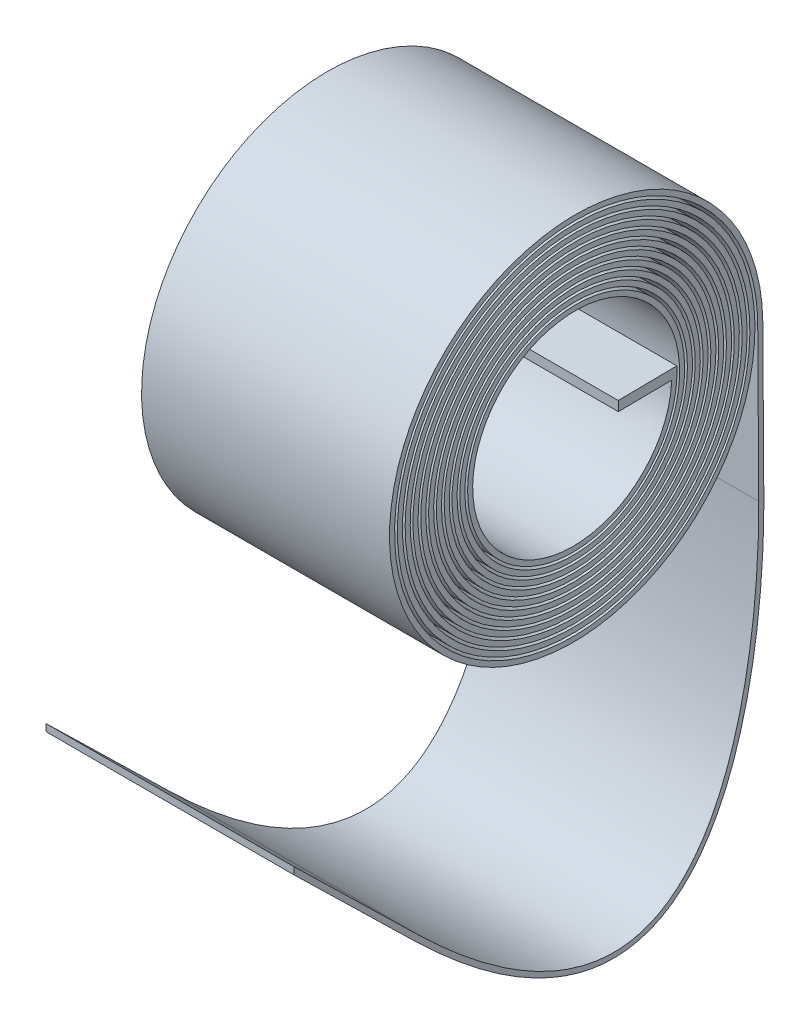
SolidWorks part; units mm, degrees
ref_plane "Front Plane" through (0, 0, 0) normal (0, 0, 1) x (1, 0, 0)
ref_plane "Top Plane" through (0, 0, 0) normal (0, 1, 0) x (1, 0, 0)
ref_plane "Right Plane" through (0, 0, 0) normal (1, 0, 0) x (0, 0, -1)
sketch "Sketch1" plane through (0, 0, 0) normal (1, 0, 0) x (0, 0, -1)
  circle A0 centre (0, 0) radius 2.5
  dimension "D1" = 5
curve "Helix/Spiral1"
sketch "Sketch2" plane through (0, 0, 0) normal (1, 0, 0) x (0, 0, -1)
  line L0 (2.5, 0) -> (2.63, 0.0017)
  line L2 (4.7, 0) -> (4.83, 0.0009)
  spline S0 degree 3 poles (-439.0072, -897.1615) (-56.85, 58.0039) (7.9525, 8.6548) (1.9311, -1.6856) (1.5943, -2.015) (0.7951, -2.4552) (0.3338, -2.5653) (-0.5842, -2.5317) (-1.0395, -2.3879) (-1.8147, -1.8837) (-2.1335, -1.5239) (-2.5418, -0.6873) (-2.6308, -0.2117) (-2.5504, 0.722) (-2.381, 1.1787) (-1.8283, 1.9431) (-1.4457, 2.2498) (-0.5729, 2.6237) (-0.084, 2.6904) (0.863, 2.5615) (1.3196, 2.366) (2.0704, 1.7647) (2.3634, 1.3597) (2.7003, 0.4521) (2.7437, -0.0491) (2.5648, -1.0068) (2.3429, -1.4619) (1.693, -2.196) (1.2659, -2.4739) (0.3252, -2.7713) (-0.1872, -2.7902) (-1.153, -2.5601) (-1.605, -2.3113) (-2.3194, -1.6131) (-2.5808, -1.1646) (-2.8362, -0.1923) (-2.8297, 0.33) (-2.5471, 1.3011) (-2.2713, 1.7484) (-1.5251, 2.4402) (-1.0557, 2.6836) (-0.0539, 2.8946) (0.4771, 2.8618) (1.4506, 2.5256) (1.8918, 2.2227) (2.5579, 1.4291) (2.7818, 0.9395) (2.9461, -0.0898) (2.8861, -0.6281) (2.4955, -1.6011) (2.1653, -2.0344) (1.3251, -2.6719) (0.8161, -2.875) (-0.2384, -2.9904) (-0.7826, -2.9024) (-1.752, -2.4566) (-2.1759, -2.0993) (-2.7817, -1.2133) (-2.9626, -0.6859) (-3.027, 0.3916) (-2.9104, 0.9402) (-2.4087, 1.9029) (-2.0244, 2.3158) (-1.0939, 2.8869) (-0.549, 3.0443) (0.549, 3.0557) (1.1004, 2.9097) (2.0533, 2.3519) (2.4534, 1.9409) (2.9869, 0.9671) (3.1195, 0.4057) (3.0762, -0.71) (2.9002, -1.2628) (2.286, -2.2026) (1.8486, -2.5884) (0.833, -3.0814) (0.2563, -3.1879) (-0.8744, -3.088) (-1.4268, -2.8817) (-2.3503, -2.2111) (-2.72, -1.7476) (-3.1697, -0.692) (-3.249, -0.1012) (-3.091, 1.0416) (-2.854, 1.592) (-2.1271, 2.4958) (-1.6382, 2.8479) (-0.5442, 3.2515) (0.0593, 3.3024) (1.2112, 3.085) (1.7579, 2.8169) (2.6387, 2.034) (2.9715, 1.5203) (3.3263, 0.3901) (3.3478, -0.2248) (3.0696, -1.3826) (2.7703, -1.9239) (1.932, -2.7784) (1.3942, -3.0903) (0.23, -3.3937) (-0.3949, -3.3848) (-1.5554, -3.0447) (-2.0895, -2.714) (-2.9142, -1.8211) (-3.2038, -1.2601) (-3.4533, -0.0641) (-3.413, 0.5691) (-3.0101, 1.7291) (-2.6481, 2.2541) (-1.7015, 3.0458) (-1.1181, 3.3114) (0.107, 3.5047) (0.7471, 3.4321) (1.903, 2.9657) (2.4172, 2.5725) (3.1726, 1.5732) (3.4126, 0.9686) (3.5474, -0.283) (3.4419, -0.9282) (2.9114, -2.0767) (2.4871, -2.5783) (1.4366, -3.294) (0.8117, -3.5071) (-0.4635, -3.5812) (-1.1121, -3.4421) (-2.2495, -2.8471) (-2.7366, -2.3921) (-3.4095, -1.2918) (-3.5943, -0.648) (-3.6057, 0.648) (-3.4324, 1.2982) (-2.7728, 2.421) (-2.2874, 2.8918) (-1.139, 3.5186) (-0.4775, 3.6737) (0.8359, 3.6206) (1.486, 3.4125) (2.5905, 2.6884) (3.0432, 2.1732) (3.6209, 0.9787) (3.7449, 0.3009) (3.6257, -1.0268) (3.3825, -1.6749) (2.5939, -2.7574) (2.0496, -3.1903) (0.811, -3.7157) (0.1184, -3.8075) (-1.2202, -3.6206) (-1.8644, -3.342) (-2.9213, -2.4894) (-3.3324, -1.9167) (-3.8027, -0.6363) (-3.8611, 0.0695) (-3.6051, 1.4156) (-3.2909, 2.0539) (-2.3751, 3.0814) (-1.7747, 3.4691) (-0.455, 3.8814) (0.2624, 3.9054) (1.6123, 3.579) (2.2428, 3.2292) (3.2373, 2.2509) (3.5998, 1.6239) (3.9513, 0.2676) (3.9398, -0.4598) (3.5423, -1.8098) (3.1567, -2.4305) (2.1171, -3.3882) (1.4645, -3.7239) (0.0743, -4.0121) (-0.6612, -3.9642) (-2.0076, -3.4946) (-2.6165, -3.0735) (-3.5338, -1.9738) (-3.8409, -1.2967) (-4.0633, 0.1242) (-3.9781, 0.8661) (-3.436, 2.2049) (-2.9796, 2.8) (-1.8213, 3.6733) (-1.121, 3.9503) (0.3277, 4.1045) (1.0739, 3.9814) (2.4013, 3.3663) (2.9806, 2.875) (3.8063, 1.6598) (4.0516, 0.9376) (4.1354, -0.5354) (3.9738, -1.2841) (3.2855, -2.5961) (2.7598, -3.1575) (1.4896, -3.9322) (0.7469, -4.1443) (-0.7469, -4.1557) (-1.4961, -3.955) (-2.7886, -3.1936) (-3.3302, -2.634) (-4.0504, -1.311) (-4.2279, -0.5494) (-4.1651, 0.9618) (-3.9249, 1.7093) (-3.0907, 2.9783) (-2.4979, 3.4981) (-1.1243, 4.1604) (-0.3455, 4.302) (1.1793, 4.1633) (1.9231, 3.8832) (3.1646, 2.9767) (3.6605, 2.3515) (4.2617, 0.93) (4.3661, 0.1356) (4.1501, -1.3989) (3.8299, -2.1368) (2.8518, -3.3467) (2.1952, -3.8169) (0.7284, -4.3539) (-0.0797, -4.4199) (-1.62, -4.1252) (-2.3499, -3.7649) (-3.5241, -2.7161) (-3.9667, -2.0291) (-4.4364, -0.52) (-4.4629, 0.3) (-4.0885, 1.842) (-3.6881, 2.5617) (-2.5698, 3.6962) (-1.8535, 4.1092) (-0.3052, 4.5089) (0.5248, 4.4949) (2.0642, 4.0398) (2.7716, 3.5994) (3.8622, 2.4131) (4.244, 1.6688) (4.5708, 0.0845) (4.5154, -0.7533) (3.9791, -2.2861) (3.499, -2.9788) (2.2462, -4.0217) (1.4753, -4.3704) (0.2627, -4.559) (-0.1504, -4.567) (-0.9645, -4.4723) (-1.3656, -4.3697) (-2.1264, -4.0607) (-2.4862, -3.8544) (-3.1383, -3.3528) (-3.4306, -3.0574) (-3.9263, -2.3988) (-4.1296, -2.0355) (-4.4321, -1.2671) (-4.5313, -0.862) (-4.6181, -0.0392) (-4.6057, 0.3785) (-4.4696, 1.1962) (-4.346, 1.5962) (-3.9961, 2.3494) (-3.7699, 2.7025) (-3.2308, 3.3363) (-2.9179, 3.6168) (-2.228, 4.0847) (-1.851, 4.272) (-1.0599, 4.5394) (-0.6458, 4.6195) (0.1896, 4.6662) (0.6108, 4.6329) (1.4299, 4.4548) (1.8277, 4.3101) (2.571, 3.9193) (2.9164, 3.6733) (3.5297, 3.0973) (3.7975, 2.7674) (4.2357, 2.0475) (4.4061, 1.6574) (9.2324, -15.3331) (-77.8687, -58.615) (-418.7177, 905.7456) knots -0.190695 -0.190695 -0.190695 -0.190695 0.007812 0.007812 0.015625 0.015625 0.023437 0.023437 0.03125 0.03125 0.039062 0.039062 0.046875 0.046875 0.054687 0.054687 0.0625 0.0625 0.070312 0.070312 0.078125 0.078125 0.085937 0.085937 0.09375 0.09375 0.101562 0.101562 0.109375 0.109375 0.117187 0.117187 0.125 0.125 0.132812 0.132812 0.140625 0.140625 0.148438 0.148438 0.15625 0.15625 0.164062 0.164062 0.171875 0.171875 0.179688 0.179688 0.1875 0.1875 0.195312 0.195312 0.203125 0.203125 0.210938 0.210938 0.21875 0.21875 0.226562 0.226562 0.234375 0.234375 0.242188 0.242188 0.25 0.25 0.257812 0.257812 0.265625 0.265625 0.273438 0.273438 0.28125 0.28125 0.289062 0.289062 0.296875 0.296875 0.304688 0.304688 0.3125 0.3125 0.320312 0.320312 0.328125 0.328125 0.335938 0.335938 0.34375 0.34375 0.351562 0.351562 0.359375 0.359375 0.367188 0.367188 0.375 0.375 0.382812 0.382812 0.390625 0.390625 0.398438 0.398438 0.40625 0.40625 0.414062 0.414062 0.421875 0.421875 0.429688 0.429688 0.4375 0.4375 0.445312 0.445312 0.453125 0.453125 0.460938 0.460938 0.46875 0.46875 0.476562 0.476562 0.484375 0.484375 0.492188 0.492188 0.5 0.5 0.507812 0.507812 0.515625 0.515625 0.523438 0.523438 0.53125 0.53125 0.539062 0.539062 0.546875 0.546875 0.554688 0.554688 0.5625 0.5625 0.570312 0.570312 0.578125 0.578125 0.585938 0.585938 0.59375 0.59375 0.601562 0.601562 0.609375 0.609375 0.617188 0.617188 0.625 0.625 0.632812 0.632812 0.640625 0.640625 0.648438 0.648438 0.65625 0.65625 0.664062 0.664062 0.671875 0.671875 0.679688 0.679688 0.6875 0.6875 0.695312 0.695312 0.703125 0.703125 0.710938 0.710938 0.71875 0.71875 0.726562 0.726562 0.734375 0.734375 0.742188 0.742188 0.75 0.75 0.757812 0.757812 0.765625 0.765625 0.773438 0.773438 0.78125 0.78125 0.789062 0.789062 0.796875 0.796875 0.804688 0.804688 0.8125 0.8125 0.820312 0.820312 0.828125 0.828125 0.835938 0.835938 0.84375 0.84375 0.851562 0.851562 0.859375 0.859375 0.867188 0.867188 0.875 0.875 0.882812 0.882812 0.890625 0.890625 0.898438 0.898438 0.90625 0.90625 0.914062 0.914062 0.921875 0.921875 0.929688 0.929688 0.933594 0.933594 0.9375 0.9375 0.941406 0.941406 0.945312 0.945312 0.949219 0.949219 0.953125 0.953125 0.957031 0.957031 0.960938 0.960938 0.964844 0.964844 0.96875 0.96875 0.972656 0.972656 0.976562 0.976562 0.980469 0.980469 0.984375 0.984375 0.988281 0.988281 0.992188 0.992188 0.996094 0.996094 1.155603 1.155603 1.155603 1.155603 only from (2.5, 0) to (4.7, 0) construction
  spline S1 degree 3 poles (2.5, 0) (2.5057, -0.45) (2.3871, -0.9025) (1.9311, -1.6856) (1.5943, -2.015) (0.7951, -2.4552) (0.3338, -2.5653) (-0.5842, -2.5317) (-1.0395, -2.3879) (-1.8147, -1.8837) (-2.1335, -1.5239) (-2.5418, -0.6873) (-2.6308, -0.2117) (-2.5504, 0.722) (-2.381, 1.1787) (-1.8283, 1.9431) (-1.4457, 2.2498) (-0.5729, 2.6237) (-0.084, 2.6904) (0.863, 2.5615) (1.3196, 2.366) (2.0704, 1.7647) (2.3634, 1.3597) (2.7003, 0.4521) (2.7437, -0.0491) (2.5648, -1.0068) (2.3429, -1.4619) (1.693, -2.196) (1.2659, -2.4739) (0.3252, -2.7713) (-0.1872, -2.7902) (-1.153, -2.5601) (-1.605, -2.3113) (-2.3194, -1.6131) (-2.5808, -1.1646) (-2.8362, -0.1923) (-2.8297, 0.33) (-2.5471, 1.3011) (-2.2713, 1.7484) (-1.5251, 2.4402) (-1.0557, 2.6836) (-0.0539, 2.8946) (0.4771, 2.8618) (1.4506, 2.5256) (1.8918, 2.2227) (2.5579, 1.4291) (2.7818, 0.9395) (2.9461, -0.0898) (2.8861, -0.6281) (2.4955, -1.6011) (2.1653, -2.0344) (1.3251, -2.6719) (0.8161, -2.875) (-0.2384, -2.9904) (-0.7826, -2.9024) (-1.752, -2.4566) (-2.1759, -2.0993) (-2.7817, -1.2133) (-2.9626, -0.6859) (-3.027, 0.3916) (-2.9104, 0.9402) (-2.4087, 1.9029) (-2.0244, 2.3158) (-1.0939, 2.8869) (-0.549, 3.0443) (0.549, 3.0557) (1.1004, 2.9097) (2.0533, 2.3519) (2.4534, 1.9409) (2.9869, 0.9671) (3.1195, 0.4057) (3.0762, -0.71) (2.9002, -1.2628) (2.286, -2.2026) (1.8486, -2.5884) (0.833, -3.0814) (0.2563, -3.1879) (-0.8744, -3.088) (-1.4268, -2.8817) (-2.3503, -2.2111) (-2.72, -1.7476) (-3.1697, -0.692) (-3.249, -0.1012) (-3.091, 1.0416) (-2.854, 1.592) (-2.1271, 2.4958) (-1.6382, 2.8479) (-0.5442, 3.2515) (0.0593, 3.3024) (1.2112, 3.085) (1.7579, 2.8169) (2.6387, 2.034) (2.9715, 1.5203) (3.3263, 0.3901) (3.3478, -0.2248) (3.0696, -1.3826) (2.7703, -1.9239) (1.932, -2.7784) (1.3942, -3.0903) (0.23, -3.3937) (-0.3949, -3.3848) (-1.5554, -3.0447) (-2.0895, -2.714) (-2.9142, -1.8211) (-3.2038, -1.2601) (-3.4533, -0.0641) (-3.413, 0.5691) (-3.0101, 1.7291) (-2.6481, 2.2541) (-1.7015, 3.0458) (-1.1181, 3.3114) (0.107, 3.5047) (0.7471, 3.4321) (1.903, 2.9657) (2.4172, 2.5725) (3.1726, 1.5732) (3.4126, 0.9686) (3.5474, -0.283) (3.4419, -0.9282) (2.9114, -2.0767) (2.4871, -2.5783) (1.4366, -3.294) (0.8117, -3.5071) (-0.4635, -3.5812) (-1.1121, -3.4421) (-2.2495, -2.8471) (-2.7366, -2.3921) (-3.4095, -1.2918) (-3.5943, -0.648) (-3.6057, 0.648) (-3.4324, 1.2982) (-2.7728, 2.421) (-2.2874, 2.8918) (-1.139, 3.5186) (-0.4775, 3.6737) (0.8359, 3.6206) (1.486, 3.4125) (2.5905, 2.6884) (3.0432, 2.1732) (3.6209, 0.9787) (3.7449, 0.3009) (3.6257, -1.0268) (3.3825, -1.6749) (2.5939, -2.7574) (2.0496, -3.1903) (0.811, -3.7157) (0.1184, -3.8075) (-1.2202, -3.6206) (-1.8644, -3.342) (-2.9213, -2.4894) (-3.3324, -1.9167) (-3.8027, -0.6363) (-3.8611, 0.0695) (-3.6051, 1.4156) (-3.2909, 2.0539) (-2.3751, 3.0814) (-1.7747, 3.4691) (-0.455, 3.8814) (0.2624, 3.9054) (1.6123, 3.579) (2.2428, 3.2292) (3.2373, 2.2509) (3.5998, 1.6239) (3.9513, 0.2676) (3.9398, -0.4598) (3.5423, -1.8098) (3.1567, -2.4305) (2.1171, -3.3882) (1.4645, -3.7239) (0.0743, -4.0121) (-0.6612, -3.9642) (-2.0076, -3.4946) (-2.6165, -3.0735) (-3.5338, -1.9738) (-3.8409, -1.2967) (-4.0633, 0.1242) (-3.9781, 0.8661) (-3.436, 2.2049) (-2.9796, 2.8) (-1.8213, 3.6733) (-1.121, 3.9503) (0.3277, 4.1045) (1.0739, 3.9814) (2.4013, 3.3663) (2.9806, 2.875) (3.8063, 1.6598) (4.0516, 0.9376) (4.1354, -0.5354) (3.9738, -1.2841) (3.2855, -2.5961) (2.7598, -3.1575) (1.4896, -3.9322) (0.7469, -4.1443) (-0.7469, -4.1557) (-1.4961, -3.955) (-2.7886, -3.1936) (-3.3302, -2.634) (-4.0504, -1.311) (-4.2279, -0.5494) (-4.1651, 0.9618) (-3.9249, 1.7093) (-3.0907, 2.9783) (-2.4979, 3.4981) (-1.1243, 4.1604) (-0.3455, 4.302) (1.1793, 4.1633) (1.9231, 3.8832) (3.1646, 2.9767) (3.6605, 2.3515) (4.2617, 0.93) (4.3661, 0.1356) (4.1501, -1.3989) (3.8299, -2.1368) (2.8518, -3.3467) (2.1952, -3.8169) (0.7284, -4.3539) (-0.0797, -4.4199) (-1.62, -4.1252) (-2.3499, -3.7649) (-3.5241, -2.7161) (-3.9667, -2.0291) (-4.4364, -0.52) (-4.4629, 0.3) (-4.0885, 1.842) (-3.6881, 2.5617) (-2.5698, 3.6962) (-1.8535, 4.1092) (-0.3052, 4.5089) (0.5248, 4.4949) (2.0642, 4.0398) (2.7716, 3.5994) (3.8622, 2.4131) (4.244, 1.6688) (4.5708, 0.0845) (4.5154, -0.7533) (3.9791, -2.2861) (3.499, -2.9788) (2.2462, -4.0217) (1.4753, -4.3704) (0.2627, -4.559) (-0.1504, -4.567) (-0.9645, -4.4723) (-1.3656, -4.3697) (-2.1264, -4.0607) (-2.4862, -3.8544) (-3.1383, -3.3528) (-3.4306, -3.0574) (-3.9263, -2.3988) (-4.1296, -2.0355) (-4.4321, -1.2671) (-4.5313, -0.862) (-4.6181, -0.0392) (-4.6057, 0.3785) (-4.4696, 1.1962) (-4.346, 1.5962) (-3.9961, 2.3494) (-3.7699, 2.7025) (-3.2308, 3.3363) (-2.9179, 3.6168) (-2.228, 4.0847) (-1.851, 4.272) (-1.0599, 4.5394) (-0.6458, 4.6195) (0.1896, 4.6662) (0.6108, 4.6329) (1.4299, 4.4548) (1.8277, 4.3101) (2.571, 3.9193) (2.9164, 3.6733) (3.5297, 3.0973) (3.7975, 2.7674) (4.2357, 2.0475) (4.4061, 1.6574) (4.6368, 0.8451) (4.6971, 0.423) (4.7, 0) knots 0 0 0 0 0.007812 0.007812 0.015625 0.015625 0.023437 0.023437 0.03125 0.03125 0.039062 0.039062 0.046875 0.046875 0.054687 0.054687 0.0625 0.0625 0.070312 0.070312 0.078125 0.078125 0.085937 0.085937 0.09375 0.09375 0.101562 0.101562 0.109375 0.109375 0.117187 0.117187 0.125 0.125 0.132812 0.132812 0.140625 0.140625 0.148438 0.148438 0.15625 0.15625 0.164062 0.164062 0.171875 0.171875 0.179688 0.179688 0.1875 0.1875 0.195312 0.195312 0.203125 0.203125 0.210938 0.210938 0.21875 0.21875 0.226562 0.226562 0.234375 0.234375 0.242188 0.242188 0.25 0.25 0.257812 0.257812 0.265625 0.265625 0.273438 0.273438 0.28125 0.28125 0.289062 0.289062 0.296875 0.296875 0.304688 0.304688 0.3125 0.3125 0.320312 0.320312 0.328125 0.328125 0.335938 0.335938 0.34375 0.34375 0.351562 0.351562 0.359375 0.359375 0.367188 0.367188 0.375 0.375 0.382812 0.382812 0.390625 0.390625 0.398438 0.398438 0.40625 0.40625 0.414062 0.414062 0.421875 0.421875 0.429688 0.429688 0.4375 0.4375 0.445312 0.445312 0.453125 0.453125 0.460938 0.460938 0.46875 0.46875 0.476562 0.476562 0.484375 0.484375 0.492188 0.492188 0.5 0.5 0.507812 0.507812 0.515625 0.515625 0.523438 0.523438 0.53125 0.53125 0.539062 0.539062 0.546875 0.546875 0.554688 0.554688 0.5625 0.5625 0.570312 0.570312 0.578125 0.578125 0.585938 0.585938 0.59375 0.59375 0.601562 0.601562 0.609375 0.609375 0.617188 0.617188 0.625 0.625 0.632812 0.632812 0.640625 0.640625 0.648438 0.648438 0.65625 0.65625 0.664062 0.664062 0.671875 0.671875 0.679688 0.679688 0.6875 0.6875 0.695312 0.695312 0.703125 0.703125 0.710938 0.710938 0.71875 0.71875 0.726562 0.726562 0.734375 0.734375 0.742188 0.742188 0.75 0.75 0.757812 0.757812 0.765625 0.765625 0.773438 0.773438 0.78125 0.78125 0.789062 0.789062 0.796875 0.796875 0.804688 0.804688 0.8125 0.8125 0.820312 0.820312 0.828125 0.828125 0.835938 0.835938 0.84375 0.84375 0.851562 0.851562 0.859375 0.859375 0.867188 0.867188 0.875 0.875 0.882812 0.882812 0.890625 0.890625 0.898438 0.898438 0.90625 0.90625 0.914062 0.914062 0.921875 0.921875 0.929688 0.929688 0.933594 0.933594 0.9375 0.9375 0.941406 0.941406 0.945312 0.945312 0.949219 0.949219 0.953125 0.953125 0.957031 0.957031 0.960938 0.960938 0.964844 0.964844 0.96875 0.96875 0.972656 0.972656 0.976562 0.976562 0.980469 0.980469 0.984375 0.984375 0.988281 0.988281 0.992188 0.992188 0.996094 0.996094 1 1 1 1
  spline S2 degree 1 poles (2.63, 0.0017) (4.83, 0.0009) knots 0 0 1 1 construction
  spline S3 degree 3 poles (2.63, 0.0017) (2.636, -0.4675) (2.3862, -1.4263) (1.3229, -2.4639) (-0.1332, -2.812) (-1.5699, -2.3583) (-2.5753, -1.2235) (-2.8559, 0.2763) (-2.322, 1.716) (-1.1163, 2.6822) (0.4241, 2.8924) (1.8622, 2.2768) (2.7848, 1.0016) (2.9212, -0.5761) (2.2228, -2.0081) (0.8794, -2.8824) (-0.7319, -2.9419) (-2.153, -2.1598) (-2.9746, -0.75) (-2.9542, 0.8911) (-2.0879, 2.2965) (-0.6137, 3.0609) (1.0533, 2.9579) (2.4381, 2.007) (3.1408, 0.4707) (2.9527, -1.2179) (1.9172, -2.5771) (0.3213, -3.214) (-1.3845, -2.9383) (-2.7131, -1.8185) (-3.28, -0.1658) (-2.9145, 1.5525) (-1.711, 2.8455) (-0.0047, 3.3383) (1.7215, 2.8812) (2.9738, 1.5948) (3.3886, -0.1618) (2.8383, -1.8909) (1.4701, -3.0974) (-0.3332, -3.4304) (-2.0602, -2.7856) (-3.2158, -1.337) (-3.4635, 0.5091) (-2.7229, 2.2287) (-1.1958, 3.3285) (0.689, 3.4874) (2.396, 2.6504) (3.435, 1.0468) (3.5019, -0.8725) (2.5679, -2.5615) (0.8901, -3.5347) (-1.059, -3.5067) (-2.7245, -2.4755) (-3.6272, -0.7261) (-3.5014, 1.248) (-2.3731, 2.8845) (-0.5552, 3.712) (1.4391, 3.486) (3.041, 2.2609) (3.7887, 0.3777) (3.4601, -1.6316) (2.1391, -3.1933) (0.1939, -3.8567) (-1.8249, -3.4236) (-3.3408, -2.0076) (-3.9157, -0.0045) (-3.3764, 2.0185) (-1.8668, 3.4831) (0.1904, 3.9653) (2.2119, 3.3183) (3.6194, 1.7167) (4.005, -0.39) (3.2492, -2.4043) (1.5578, -3.7493) (-0.594, -4.0346) (-2.5952, -3.1691) (-3.8722, -1.3902) (-4.0537, 0.8019) (-3.0781, 2.7839) (-1.2142, 3.9875) (1.013, 4.0619) (2.9699, 2.976) (4.0948, 1.0302) (4.0591, -1.2268) (2.8631, -3.1524) (0.8386, -4.1935) (-1.4427, -4.045) (-3.331, -2.7393) (-4.2832, -0.6397) (-4.0194, 1.6602) (-2.6048, 3.5048) (-0.4341, 4.3633) (1.8786, 3.982) (3.6735, 2.4597) (4.4334, 0.2221) (3.9327, -2.0972) (2.3043, -3.8362) (0.0043, -4.4931) (-2.3155, -3.8715) (-3.9923, -2.1388) (-4.5419, 0.2188) (-3.7982, 2.5328) (-1.9635, 4.1414) (0.4468, 4.5796) (2.7483, 3.7129) (4.2828, 1.7786) (4.6057, -0.6789) (3.6154, -2.9616) (1.5845, -4.4159) (-0.9146, -4.6199) (-3.1717, -3.5058) (-4.5401, -1.3817) (-4.622, 1.1534) (-3.3842, 3.3782) (-1.1704, 4.6549) (1.3945, 4.6116) (3.5803, 3.2507) (4.7599, 0.9511) (4.5886, -1.6374) (3.1055, -3.7774) (0.7243, -4.8543) (-1.8813, -4.5527) (-3.9687, -2.9486) (-4.9379, -0.4906) (-4.5039, 2.1256) (-2.7804, 4.1535) (-0.2503, 5.0105) (2.3695, 4.4404) (4.3314, 2.6064) (4.8242, 0.8582) (4.83, 0.0009) knots 0 0 0 0 0.007812 0.015625 0.023438 0.03125 0.039062 0.046875 0.054688 0.0625 0.070312 0.078125 0.085938 0.09375 0.101562 0.109375 0.117188 0.125 0.132812 0.140625 0.148438 0.15625 0.164062 0.171875 0.179688 0.1875 0.195312 0.203125 0.210938 0.21875 0.226562 0.234375 0.242188 0.25 0.257812 0.265625 0.273438 0.28125 0.289062 0.296875 0.304688 0.3125 0.320312 0.328125 0.335938 0.34375 0.351562 0.359375 0.367188 0.375 0.382812 0.390625 0.398438 0.40625 0.414062 0.421875 0.429688 0.4375 0.445312 0.453125 0.460938 0.46875 0.476562 0.484375 0.492188 0.5 0.507812 0.515625 0.523438 0.53125 0.539062 0.546875 0.554688 0.5625 0.570312 0.578125 0.585938 0.59375 0.601562 0.609375 0.617188 0.625 0.632812 0.640625 0.648438 0.65625 0.664062 0.671875 0.679688 0.6875 0.695312 0.703125 0.710938 0.71875 0.726562 0.734375 0.742188 0.75 0.757812 0.765625 0.773438 0.78125 0.789062 0.796875 0.804688 0.8125 0.820312 0.828125 0.835938 0.84375 0.851562 0.859375 0.867188 0.875 0.882812 0.890625 0.898438 0.90625 0.914062 0.921875 0.929688 0.9375 0.945312 0.953125 0.960938 0.96875 0.976562 0.984375 0.992188 1 1 1 1
  dimension "D1" = 0.13
extrude "Boss-Extrude1" add sketch "Sketch2" along normal mid plane 6.35
sketch "Sketch3" plane through (0, 0, 0) normal (1, 0, 0) x (0, 0, -1)
  circle A0 centre (0, 0) radius 4.83 construction
sketch "Sketch4" plane through (0, 0, 0) normal (1, 0, 0) x (0, 0, -1)
  line L0 (2.5, 0) -> (1.1301, -0.0174) construction
  line L5 (2.6316, -0.1233) -> (2.6284, 0.1266)
  line L6 (2.6284, 0.1266) -> (1.1285, 0.1075)
  line L7 (1.1285, 0.1075) -> (1.1317, -0.1424)
  line L8 (2.63, 0.0017) -> (2.5, 0) construction
  line L9 (2.6316, -0.1233) -> (1.1317, -0.1424)
  point P13 (2.63, 0.0017)
  dimension "D1" = 0.25
  dimension "D2" = 1.5
extrude "Boss-Extrude2" add sketch "Sketch4" along normal up to surface (3.175 mm away) and the other way up to surface (3.175 mm away) up to face at (3.175, 0.0005, -3.665) other way up to face at (-3.175, 0.0005, -3.665)
sketch "Sketch5" plane through (0, 0, 0) normal (1, 0, 0) x (0, 0, -1)
  line L0 (4.83, 0.0009) -> (4.8566, -3.928)
  line L1 (4.7, 0) -> (4.83, 0.0009) construction
  line L2 (4.83, 0.0009) -> (4.7, 0)
  line L3 (4.7, 0) -> (4.7266, -3.9289)
  line L4 (-4.0272, -9.15) -> (-4.118, -9.2431)
  spline S0 degree 3 poles (4.8566, -3.928) (4.8835, -7.9134) (3.6682, -16.8335) (-4.118, -9.2431) knots 0 0 0 0 1 1 1 1
  spline S1 degree 1 poles (4.7266, -3.9289) (-4.0272, -9.15) knots 0 0 1 1 construction
  spline S2 degree 3 poles (4.7266, -3.9289) (4.7284, -4.1938) (4.7219, -4.7017) (4.6605, -5.8928) (4.4724, -7.4902) (4.0086, -9.37) (3.2488, -10.9444) (2.1573, -11.9572) (0.9261, -12.1712) (-0.3258, -11.8399) (-1.4029, -11.3015) (-2.4263, -10.5774) (-3.3091, -9.8304) (-3.7964, -9.3749) (-4.0272, -9.15) knots 0 0 0 0 0.0625 0.125 0.25 0.375 0.5 0.625 0.75 0.8125 0.875 0.9375 0.96875 1 1 1 1
extrude "Boss-Extrude3" add sketch "Sketch5" along normal up to surface and the other way up to surface up to face at (3.175, -0.0349, -2.7721) other way up to face at (-3.175, -0.0349, -2.7721)
sketch "Sketch6" plane through (0, 0, 0) normal (1, 0, 0) x (0, 0, -1)
  line L0 (-4.0272, -9.15) -> (-4.118, -9.2431)
  line L1 (-4.118, -9.2431) -> (-7.1708, -6.267)
  line L2 (-7.1708, -6.267) -> (-7.1731, -6.0832)
  line L3 (-7.1731, -6.0832) -> (-4.0272, -9.15)
  line L4 (-4.0272, -9.15) -> (-4.118, -9.2431) construction
  line L5 (-7.1731, -6.0832) -> (-4.0272, -9.15) construction
  point P7 (0, 0)
  point P9 (0, 0)
  point P11 (0, 0)
  point P13 (0, 0)
  point P15 (0, 0)
extrude "Boss-Extrude4" add sketch "Sketch6" along normal up to surface and the other way up to surface up to face at (3.175, -2.2147, -1.9587) other way up to face at (-3.175, -2.2069, -1.9771)
